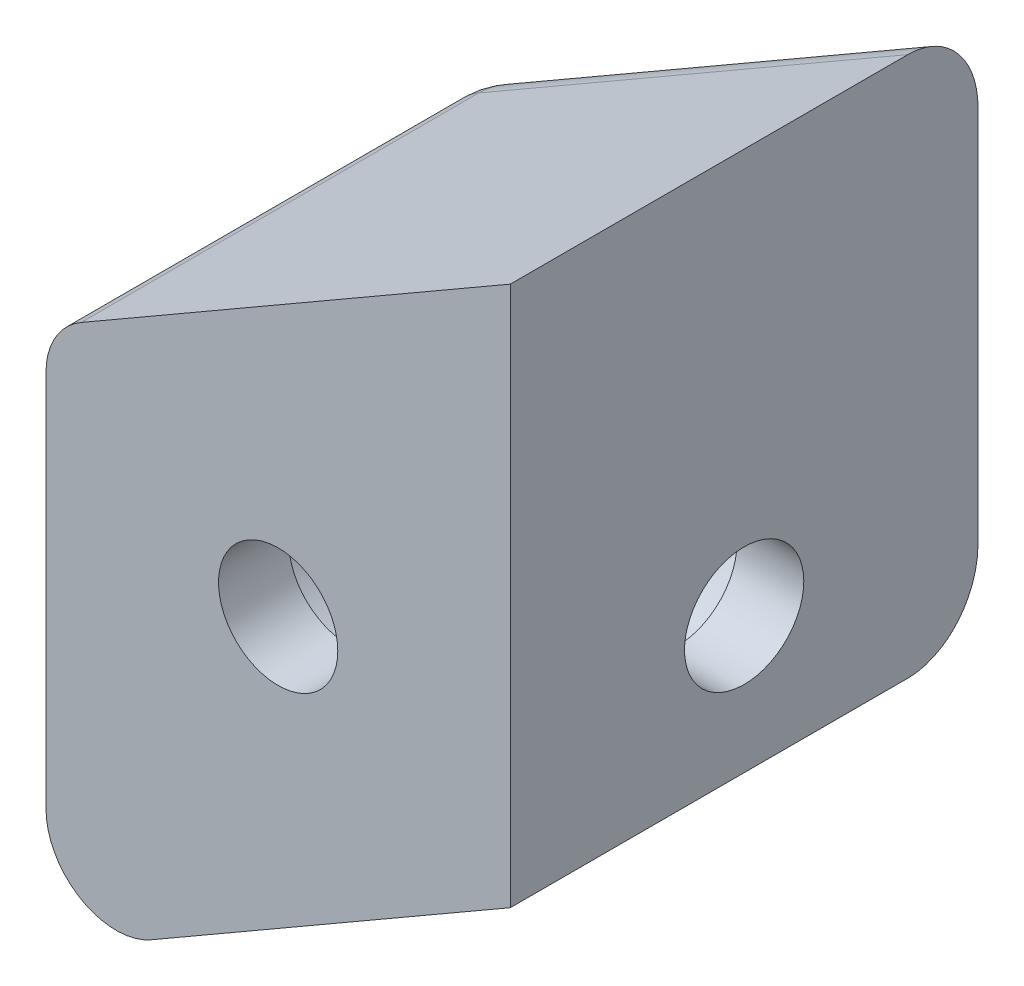
SolidWorks part; units mm, degrees
ref_plane "Front Plane" through (0, 0, 0) normal (0, 0, 1) x (1, 0, 0)
ref_plane "Top Plane" through (0, 0, 0) normal (0, 1, 0) x (1, 0, 0)
ref_plane "Right Plane" through (0, 0, 0) normal (1, 0, 0) x (0, 0, -1)
sketch "Sketch1" plane through (0, 0, 0) normal (0, 0, 1) x (1, 0, 0)
  line L0 (-10, 13.094) -> (9.8544, 24.557)
  line L6 (-10, -10) -> (-10, 13.094)
  line L10 (-10, -10) -> (9.8544, 1.463)
  line L11 (9.8544, 1.463) -> (9.8544, 24.557)
  point P0 (0, 0)
extrude "Boss-Extrude1" add sketch "Sketch1" along normal blind 20
sketch "Sketch4" plane through (0, 0, 0) normal (0, 0, 1) x (1, 0, 0)
  line L0 (-0.0728, 18.8255) -> (-0.0728, -4.2685) construction
  line L1 (9.8544, 24.557) -> (-10, 13.094) construction
  line L2 (-10, -10) -> (9.8544, 1.463) construction
  circle A2 centre (-0.0728, 7.2785) radius 2.55
extrude "Cut-Extrude2" cut sketch "Sketch4" along normal through all
sketch "Sketch5" plane through (0, 0, 0) normal (1, 0, 0) x (0, 0, -1)
  line L0 (-10, 24.557) -> (-10, -10) construction
  line L1 (-20, 24.557) -> (0, 24.557) construction
  circle A0 centre (-10, 7.2785) radius 2.55
extrude "Cut-Extrude3" cut sketch "Sketch5" against normal through all both and the other way through all
sketch "Sketch6" plane through (0, 0, 0) normal (0, 0, 1) x (1, 0, 0)
  circle A1 centre (-0.0728, 7.2785) radius 5.3
extrude "Cut-Extrude4" cut sketch "Sketch6" along normal blind 17 from surface starting at face at (2.4772, 7.2785, 0)
sketch "Sketch7" plane through (0, 0, 0) normal (1, 0, 0) x (0, 0, -1)
  circle A0 centre (-10, 7.2785) radius 5.3
extrude "Cut-Extrude5" cut sketch "Sketch7" against normal blind 10 and the other way blind 7
fillet "Fillet1" radius 0.7 2 edges at (7, 7.2785, 4.7) (5.2272, 7.2785, 17)
fillet "Fillet2" radius 3 5 edges at (-10, -10, 10) (-10, 13.094, 10) (-0.0728, 18.8255, 0) (-10, 1.547, 0) (-0.0728, -4.2685, 0)
